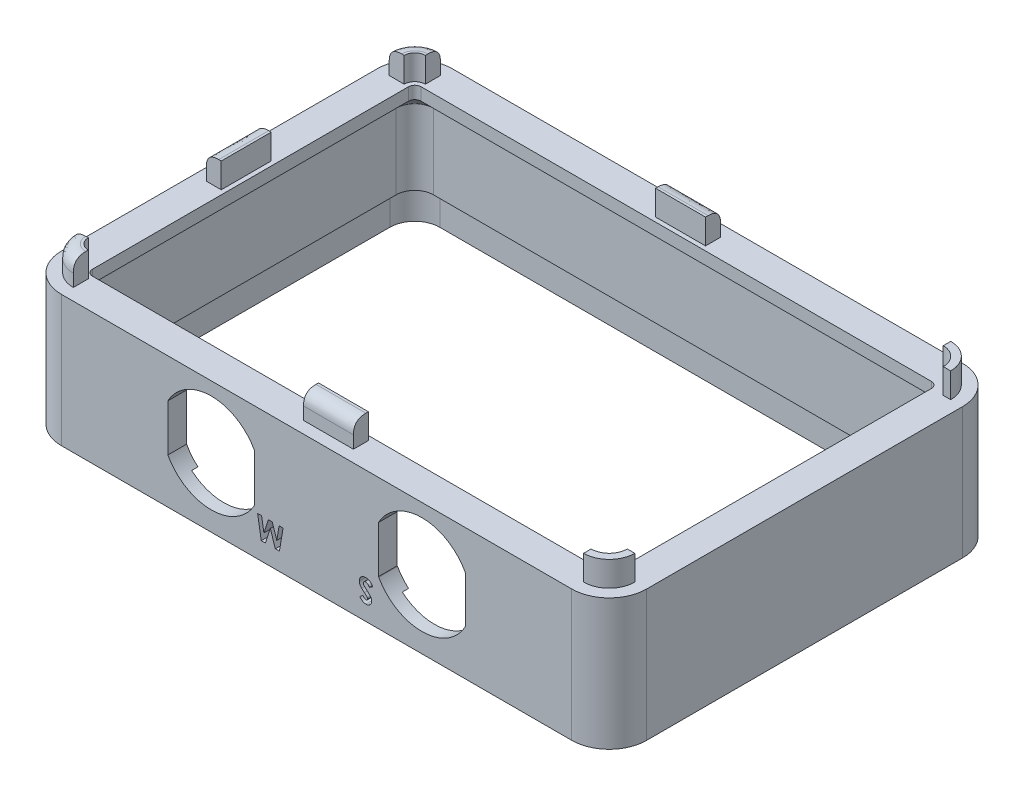
SolidWorks part; units mm, degrees
ref_plane "Alzado" through (0, 0, 0) normal (0, 0, 1) x (1, 0, 0)
ref_plane "Planta" through (0, 0, 0) normal (0, 1, 0) x (1, 0, 0)
ref_plane "Vista lateral" through (0, 0, 0) normal (1, 0, 0) x (0, 0, -1)
sketch "Croquis1" plane through (0, 0, 0) normal (0, 1, 0) x (1, 0, 0)
  line L1 (-40.87, -31.3) -> (40.87, -31.3)
  line L2 (-46.87, -25.3) -> (-46.87, 25.3)
  line L3 (-40.87, 31.3) -> (40.87, 31.3)
  line L4 (46.87, -25.3) -> (46.87, 25.3)
  line L5 (-46.87, -31.3) -> (46.87, 31.3) construction
  line L6 (-46.87, 31.3) -> (46.87, -31.3) construction
  arc A0 (40.87, -31.3) -> (46.87, -25.3) centre (40.87, -25.3) ccw
  arc A1 (40.87, 31.3) -> (46.87, 25.3) centre (40.87, 25.3) cw
  arc A2 (-46.87, 25.3) -> (-40.87, 31.3) centre (-40.87, 25.3) cw
  arc A3 (-40.87, -31.3) -> (-46.87, -25.3) centre (-40.87, -25.3) cw
  point P0 (0, 0)
  dimension "D3" = 6
  dimension "D1" = 62.6
  dimension "D2" = 93.74
extrude "Saliente-Extruir1" add sketch "Croquis1" along normal blind 2
sketch "Croquis2" plane through (0, 2, 0) normal (0, 1, 0) x (1, 0, 0)
  line L0 (-40.87, 25.3) -> (-40.87, 28.8) construction
  line L1 (-40.87, 28.8) -> (-40.87, 25.3) construction
  line L2 (-40.87, 25.3) -> (-44.37, 25.3) construction
  line L3 (-43.77, 25.3) -> (-44.97, 25.3) construction
  line L4 (-40.87, 29.4) -> (-40.87, 28.2) construction
  line L5 (0, 0) -> (-46.87, 0) construction
  line L6 (-46.87, 25.3) -> (-46.87, -25.3) construction
  line L7 (0, 0) -> (0, 31.3) construction
  line L8 (40.87, 31.3) -> (-40.87, 31.3) construction
  line L11 (43.77, 25.3) -> (44.97, 25.3)
  line L12 (40.87, 29.4) -> (40.87, 28.2)
  line L15 (-40.87, 29.4) -> (-40.87, 27)
  line L16 (-44.97, 25.3) -> (-42.57, 25.3)
  line L17 (-40.87, -29.4) -> (-40.87, -27)
  line L18 (-44.97, -25.3) -> (-42.57, -25.3)
  line L19 (-44.97, -25.3) -> (-44.97, 25.3) construction
  line L20 (-42.57, -25.3) -> (-42.57, 25.3) construction
  line L21 (-40.87, 27) -> (0, 27) construction
  line L22 (-44.97, -4) -> (-42.57, -4)
  line L23 (-44.97, -4) -> (-44.97, 4)
  line L24 (-44.97, 4) -> (-42.57, 4)
  line L25 (-42.57, -4) -> (-42.57, 4)
  line L26 (-40.87, 29.4) -> (0, 29.4) construction
  line L27 (-4, -29.4) -> (4, -29.4)
  line L28 (-4, 27) -> (4, 27)
  line L29 (-4, 27) -> (-4, 29.4)
  line L30 (-4, 29.4) -> (4, 29.4)
  line L31 (4, 27) -> (4, 29.4)
  line L32 (4, -27) -> (4, -29.4)
  line L33 (-4, -27) -> (4, -27)
  line L34 (-4, -27) -> (-4, -29.4)
  line L35 (43.77, -25.3) -> (44.97, -25.3)
  line L36 (40.87, -29.4) -> (40.87, -28.2)
  arc A0 (-44.37, 25.3) -> (-40.87, 28.8) centre (-40.87, 25.3) cw
  arc A1 (-43.77, 25.3) -> (-40.87, 28.2) centre (-40.87, 25.3) cw construction
  arc A2 (-44.97, 25.3) -> (-40.87, 29.4) centre (-40.87, 25.3) cw
  arc A5 (44.97, 25.3) -> (40.87, 29.4) centre (40.87, 25.3) ccw
  arc A6 (43.77, 25.3) -> (40.87, 28.2) centre (40.87, 25.3) ccw
  arc A9 (-40.87, 27) -> (-42.57, 25.3) centre (-40.87, 25.3) ccw
  arc A10 (-44.97, -25.3) -> (-40.87, -29.4) centre (-40.87, -25.3) ccw
  arc A11 (-40.87, -27) -> (-42.57, -25.3) centre (-40.87, -25.3) cw
  arc A12 (43.77, -25.3) -> (40.87, -28.2) centre (40.87, -25.3) cw
  circle A13 centre (-40.87, 25.3) radius 6 construction
  circle A14 centre (-40.87, 25.3) radius 3.5 construction
  arc A15 (44.97, -25.3) -> (40.87, -29.4) centre (40.87, -25.3) cw
  point P41 (-44.97, 0)
  point P52 (0, 27)
  dimension "D1" = 2.5
  dimension "D4" = 1.8
  dimension "D5" = 8
  dimension "D6" = 8
  dimension "D2" = 0.6
  dimension "D3" = 0.6
extrude "Saliente-Extruir2" add sketch "Croquis2" along normal blind 4 contours A6 L11 A5 L12 | A2 L3 A0 L4 | L3 A1 L4 A0 | A10 L17 A11 L18 | A12 L36 A15 L35 | L27 L32 L33 L34 | L23 L22 L25 L24 | L29 L28 L31 L30 region at (43.12, 2, -27.55) region at (-40.928, 2, -29.1) region at (-42.5913, 2, -27.0213)
sketch "Croquis3" plane through (0, 2, 0) normal (0, 1, 0) x (1, 0, 0)
  line L8 (41.87, -25.3) -> (41.87, 25.3)
  line L9 (40.87, 26.3) -> (-40.87, 26.3)
  line L10 (-41.87, 25.3) -> (-41.87, -25.3)
  line L11 (-40.87, -26.3) -> (40.87, -26.3)
  line L12 (41.87, -25.3) -> (41.87, 25.3)
  line L13 (40.87, 26.3) -> (-40.87, 26.3)
  line L14 (-41.87, 25.3) -> (-41.87, -25.3)
  line L15 (-40.87, -26.3) -> (40.87, -26.3)
  arc A8 (40.87, -26.3) -> (41.87, -25.3) centre (40.87, -25.3) ccw
  arc A9 (41.87, 25.3) -> (40.87, 26.3) centre (40.87, 25.3) ccw
  arc A10 (-40.87, 26.3) -> (-41.87, 25.3) centre (-40.87, 25.3) ccw
  arc A11 (-41.87, -25.3) -> (-40.87, -26.3) centre (-40.87, -25.3) ccw
  arc A12 (40.87, -26.3) -> (41.87, -25.3) centre (40.87, -25.3) ccw
  arc A13 (41.87, 25.3) -> (40.87, 26.3) centre (40.87, 25.3) ccw
  arc A14 (-40.87, 26.3) -> (-41.87, 25.3) centre (-40.87, 25.3) ccw
  arc A15 (-41.87, -25.3) -> (-40.87, -26.3) centre (-40.87, -25.3) ccw
  dimension "D2" = 83.74
  dimension "D3" = 52.6
  dimension "D1" = 5
extrude "Cortar-Extruir1" cut sketch "Croquis3" against normal blind 10
sketch "Croquis4" plane through (0, 0, 0) normal (0, -1, 0) x (1, 0, 0)
  line L0 (-43.87, 25.3) -> (-43.87, -25.3)
  line L1 (-40.87, -28.3) -> (40.87, -28.3)
  line L2 (43.87, -25.3) -> (43.87, 25.3)
  line L3 (40.87, 28.3) -> (-40.87, 28.3)
  line L8 (40.87, 31.3) -> (-40.87, 31.3)
  line L9 (-46.87, 25.3) -> (-46.87, -25.3)
  line L10 (-40.87, -31.3) -> (40.87, -31.3)
  line L11 (46.87, -25.3) -> (46.87, 25.3)
  line L12 (40.87, 31.3) -> (-40.87, 31.3)
  line L13 (-46.87, 25.3) -> (-46.87, -25.3)
  line L14 (-40.87, -31.3) -> (40.87, -31.3)
  line L15 (46.87, -25.3) -> (46.87, 25.3)
  arc A0 (-43.87, -25.3) -> (-40.87, -28.3) centre (-40.87, -25.3) ccw
  arc A1 (40.87, -28.3) -> (43.87, -25.3) centre (40.87, -25.3) ccw
  arc A2 (43.87, 25.3) -> (40.87, 28.3) centre (40.87, 25.3) ccw
  arc A3 (-40.87, 28.3) -> (-43.87, 25.3) centre (-40.87, 25.3) ccw
  arc A8 (46.87, 25.3) -> (40.87, 31.3) centre (40.87, 25.3) ccw
  arc A9 (-40.87, 31.3) -> (-46.87, 25.3) centre (-40.87, 25.3) ccw
  arc A10 (-46.87, -25.3) -> (-40.87, -31.3) centre (-40.87, -25.3) ccw
  arc A11 (40.87, -31.3) -> (46.87, -25.3) centre (40.87, -25.3) ccw
  arc A12 (46.87, 25.3) -> (40.87, 31.3) centre (40.87, 25.3) ccw
  arc A13 (-40.87, 31.3) -> (-46.87, 25.3) centre (-40.87, 25.3) ccw
  arc A14 (-46.87, -25.3) -> (-40.87, -31.3) centre (-40.87, -25.3) ccw
  arc A15 (40.87, -31.3) -> (46.87, -25.3) centre (40.87, -25.3) ccw
  dimension "D1" = 0
  dimension "D2" = 3
extrude "Saliente-Extruir3" add sketch "Croquis4" along normal blind 19
sketch "Croquis5" plane through (0, -19, 0) normal (0, -1, 0) x (1, 0, 0)
  line L8 (40.87, 29.3) -> (-40.87, 29.3)
  line L9 (-44.87, 25.3) -> (-44.87, -25.3)
  line L10 (-40.87, -29.3) -> (40.87, -29.3)
  line L11 (44.87, -25.3) -> (44.87, 25.3)
  line L12 (40.87, 29.3) -> (-40.87, 29.3)
  line L13 (-44.87, 25.3) -> (-44.87, -25.3)
  line L14 (-40.87, -29.3) -> (40.87, -29.3)
  line L15 (44.87, -25.3) -> (44.87, 25.3)
  line L20 (40.87, 28.3) -> (-40.87, 28.3)
  line L21 (-43.87, 25.3) -> (-43.87, -25.3)
  line L22 (-40.87, -28.3) -> (40.87, -28.3)
  line L23 (43.87, -25.3) -> (43.87, 25.3)
  line L24 (40.87, 28.3) -> (-40.87, 28.3)
  line L25 (-43.87, 25.3) -> (-43.87, -25.3)
  line L26 (-40.87, -28.3) -> (40.87, -28.3)
  line L27 (43.87, -25.3) -> (43.87, 25.3)
  arc A8 (44.87, 25.3) -> (40.87, 29.3) centre (40.87, 25.3) ccw
  arc A9 (-40.87, 29.3) -> (-44.87, 25.3) centre (-40.87, 25.3) ccw
  arc A10 (-44.87, -25.3) -> (-40.87, -29.3) centre (-40.87, -25.3) ccw
  arc A11 (40.87, -29.3) -> (44.87, -25.3) centre (40.87, -25.3) ccw
  arc A12 (44.87, 25.3) -> (40.87, 29.3) centre (40.87, 25.3) ccw
  arc A13 (-40.87, 29.3) -> (-44.87, 25.3) centre (-40.87, 25.3) ccw
  arc A14 (-44.87, -25.3) -> (-40.87, -29.3) centre (-40.87, -25.3) ccw
  arc A15 (40.87, -29.3) -> (44.87, -25.3) centre (40.87, -25.3) ccw
  arc A20 (43.87, 25.3) -> (40.87, 28.3) centre (40.87, 25.3) ccw
  arc A21 (-40.87, 28.3) -> (-43.87, 25.3) centre (-40.87, 25.3) ccw
  arc A22 (-43.87, -25.3) -> (-40.87, -28.3) centre (-40.87, -25.3) ccw
  arc A23 (40.87, -28.3) -> (43.87, -25.3) centre (40.87, -25.3) ccw
  arc A24 (43.87, 25.3) -> (40.87, 28.3) centre (40.87, 25.3) ccw
  arc A25 (-40.87, 28.3) -> (-43.87, 25.3) centre (-40.87, 25.3) ccw
  arc A26 (-43.87, -25.3) -> (-40.87, -28.3) centre (-40.87, -25.3) ccw
  arc A27 (40.87, -28.3) -> (43.87, -25.3) centre (40.87, -25.3) ccw
  dimension "D1" = 2
  dimension "D2" = 3
extrude "Cortar-Extruir2" cut sketch "Croquis5" against normal blind 5
fillet "Redondeo1" radius 2 8 edges at (43.87, 0, 0) (42.9913, 0, 27.4213) (42.9913, 0, -27.4213) (0, 0, 28.3) (0, 0, -28.3) (-42.9913, 0, 27.4213) (-42.9913, 0, -27.4213) (-43.87, 0, 0) conic rho 0.1
sketch "Croquis6" plane through (0, 0, 31.3) normal (0, 0, 1) x (1, 0, 0)
  line L0 (-16.87, 2) -> (-16.87, -18) construction
  line L1 (-9.9568, -11.8233) -> (-9.92, -11.756)
  line L2 (-9.92, -11.756) -> (-9.92, -4.244)
  line L3 (-16.87, -8) -> (-9.92, -8) construction
  line L4 (-23.82, -11.756) -> (-23.82, -4.244)
  line L5 (-40.87, 2) -> (40.87, 2) construction
  line L8 (-46.87, 2) -> (-46.87, -19) construction
  line L9 (0, 2) -> (0, -19) construction
  line L10 (40.87, -19) -> (-40.87, -19) construction
  line L11 (23.82, -11.756) -> (23.82, -4.244)
  line L12 (9.92, -11.756) -> (9.92, -4.244)
  line L13 (9.9568, -11.8233) -> (9.92, -11.756)
  arc A0 (-23.82, -11.756) -> (-9.9568, -11.8233) centre (-16.87, -8) ccw
  arc A1 (-9.92, -4.244) -> (-23.82, -4.244) centre (-16.87, -8) ccw
  arc A2 (23.82, -11.756) -> (9.9568, -11.8233) centre (16.87, -8) cw
  arc A3 (9.92, -4.244) -> (23.82, -4.244) centre (16.87, -8) cw
  text T0 "<b><r180>S</r></b>" font "Century Gothic" height 3.5
  text T1 "<b><r180>M</r></b>"
  dimension "D1" = 15.8
  dimension "D2" = 13.9
  dimension "D3" = 0.0767
  dimension "D4" = 10
  dimension "D5" = 30
extrude "Cortar-Extruir3" cut sketch "Croquis6" against normal blind 10
fillet "Redondeo2" radius 2 5 edges at (-43.7691, 6, -28.1991) (-43.7691, 6, 28.1991) (0, 6, -29.4) (0, 6, 29.4) (-44.97, 6, 0) conic rho 0.5
